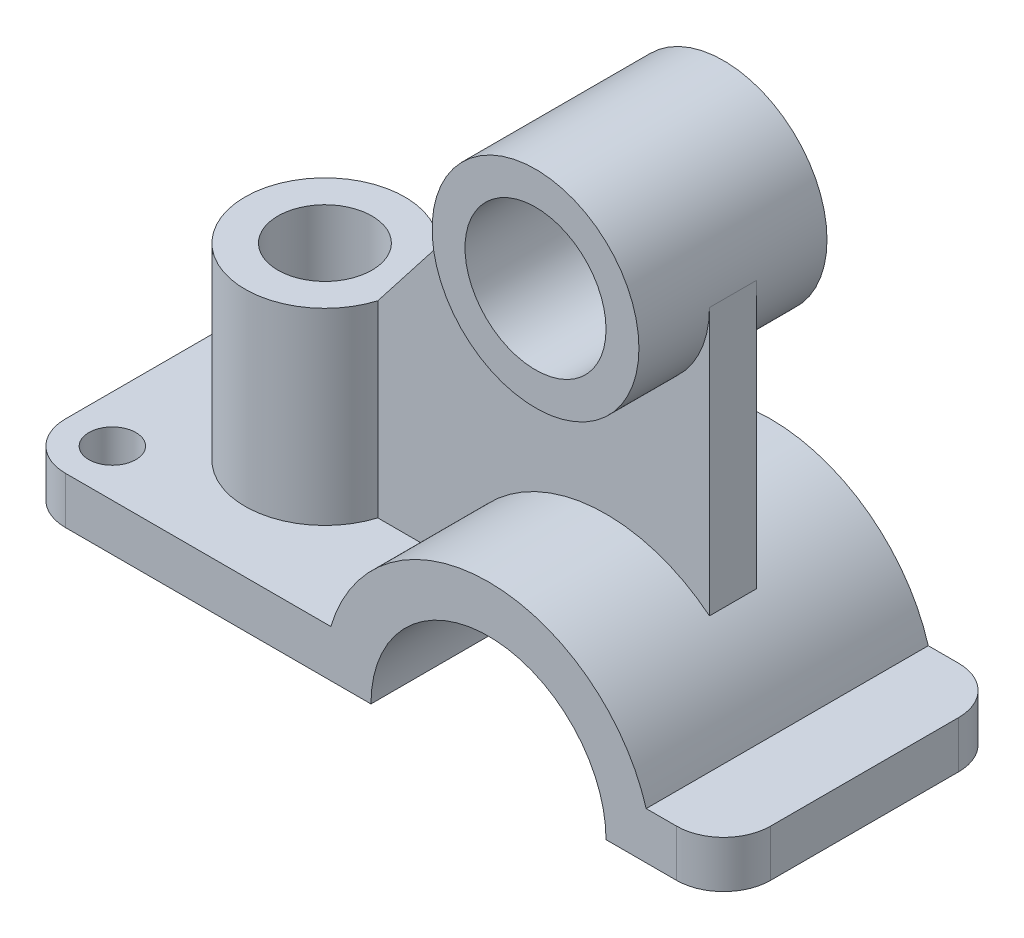
SolidWorks part; units mm, degrees
ref_plane "Front Plane" through (0, 0, 0) normal (0, 0, 1) x (1, 0, 0)
ref_plane "Top Plane" through (0, 0, 0) normal (0, 1, 0) x (1, 0, 0)
ref_plane "Right Plane" through (0, 0, 0) normal (1, 0, 0) x (0, 0, -1)
sketch "Sketch1" plane through (0, 0, 0) normal (0, 0, 1) x (1, 0, 0)
  line L0 (-163.5782, 100) -> (-163.5782, 20)
  line L1 (-180, 0) -> (-200, 0)
  line L2 (-200, 0) -> (-200, 20)
  line L3 (-200, 20) -> (-180, 20)
  line L4 (80, 20) -> (67.082, 20)
  line L5 (-67.082, 20) -> (-180, 20)
  line L6 (50, 0) -> (80, 0)
  line L7 (-180, 0) -> (-50, 0)
  line L8 (100, 20) -> (100, 0)
  line L9 (80, 20) -> (100, 20)
  line L10 (100, 0) -> (80, 0)
  line L11 (-163.5782, 100) -> (-97.082, 100)
  line L12 (-97.082, 20) -> (-97.082, 100)
  line L13 (-97.082, 100) -> (-44, 168.0524)
  line L14 (44, 168.0524) -> (44, 54.4426)
  line L15 (-190, 20) -> (-190, 0) construction
  line L16 (-170, 0) -> (-170, 20) construction
  line L17 (-109.5782, 0) -> (-109.5782, 100) construction
  line L18 (-149.5782, 100) -> (-149.5782, 0) construction
  arc A0 (67.082, 20) -> (-67.082, 20) centre (0, 0) ccw
  arc A1 (50, 0) -> (-50, 0) centre (0, 0) ccw
  circle A2 centre (0, 168.0524) radius 44
  circle A3 centre (0, 168.0524) radius 30
sketch "Sketch2" plane through (0, 0, 0) normal (0, 1, 0) x (1, 0, 0)
  line L0 (-44, -10) -> (-44, -40)
  line L1 (-44, 40) -> (-44, 10)
  line L2 (44, 10) -> (44, 40)
  line L3 (44, -40) -> (44, -10)
  line L4 (44, -40) -> (-44, -40)
  line L5 (-44, -10) -> (-44, 10)
  line L6 (44, -10) -> (44, 10)
  line L7 (44, 40) -> (-44, 40)
  line L8 (-97.082, -10) -> (-44, -10)
  line L9 (-97.082, -10) -> (-97.082, 10)
  line L10 (-97.082, 10) -> (-44, 10)
  line L11 (-67.082, 10) -> (-67.082, 60)
  line L12 (67.082, 60) -> (-67.082, 60)
  line L13 (67.082, -60) -> (67.082, 60)
  line L14 (67.082, -60) -> (-67.082, -60)
  line L15 (-67.082, -60) -> (-67.082, -10)
  line L16 (-200, -40) -> (-200, 40)
  line L17 (-67.082, -60) -> (-180, -60)
  line L18 (-67.082, 60) -> (-180, 60)
  line L19 (100, -40) -> (100, 40)
  line L20 (80, -60) -> (67.082, -60)
  line L21 (80, 60) -> (67.082, 60)
  line L22 (-44, 10) -> (44, 10) construction
  line L23 (-44, -10) -> (44, -10) construction
  line L24 (-50, -60) -> (-50, 60) construction
  line L25 (50, -60) -> (50, 60) construction
  line L26 (-30, 40) -> (-30, -40) construction
  line L27 (30, -40) -> (30, 40) construction
  line L28 (0, 10) -> (0, -10) construction
  circle A0 centre (-129.5782, 0) radius 20
  arc A1 (-97.082, 10) -> (-97.082, -10) centre (-129.5782, 0) ccw
  arc A2 (-200, -40) -> (-180, -60) centre (-180, -40) ccw
  arc A3 (-180, 60) -> (-200, 40) centre (-180, 40) ccw
  circle A4 centre (-180, 40) radius 10
  circle A5 centre (-180, -40) radius 10
  arc A6 (80, -60) -> (100, -40) centre (80, -40) ccw
  arc A7 (100, 40) -> (80, 60) centre (80, 40) ccw
sketch "Sketch3" plane through (0, 0, 0) normal (1, 0, 0) x (0, 0, -1)
  line L0 (34, 20) -> (34, 100)
  line L1 (-34, 100) -> (-34, 20)
  line L2 (-34, 70) -> (-60, 70)
  line L3 (60, 70) -> (34, 70)
  line L4 (10, 124.0524) -> (40, 124.0524)
  line L5 (-40, 124.0524) -> (-10, 124.0524)
  line L6 (40, 212.0524) -> (-40, 212.0524)
  line L7 (40, 0) -> (-40, 0)
  line L8 (40, 20) -> (-40, 20)
  line L9 (-60, 0) -> (-60, 20)
  line L10 (-60, 20) -> (-40, 20)
  line L11 (-40, 0) -> (-60, 0)
  line L12 (60, 20) -> (60, 0)
  line L13 (40, 20) -> (60, 20)
  line L14 (60, 0) -> (40, 0)
  line L15 (-34, 100) -> (34, 100)
  line L16 (10, 168.0524) -> (-10, 168.0524)
  line L17 (-10, 100) -> (-10, 168.0524)
  line L18 (10, 100) -> (10, 168.0524)
  line L19 (60, 70) -> (60, 20)
  line L20 (-60, 70) -> (-60, 20)
  line L21 (-40, 212.0524) -> (-40, 124.0524)
  line L22 (40, 212.0524) -> (40, 124.0524)
  line L23 (-10, 20) -> (-10, 100) construction
  line L24 (10, 20) -> (10, 100) construction
  line L25 (10, 54.4426) -> (-10, 54.4426) construction
  line L26 (-50, 20) -> (-50, 0) construction
  line L27 (-30, 0) -> (-30, 20) construction
  line L28 (30, 20) -> (30, 0) construction
  line L29 (50, 0) -> (50, 20) construction
  line L30 (20, 0) -> (20, 100) construction
  line L31 (-20, 100) -> (-20, 0) construction
  line L32 (-10, 70) -> (-34, 70) construction
  line L33 (34, 70) -> (10, 70) construction
  line L34 (60, 50) -> (-60, 50) construction
  line L35 (-40, 138.0524) -> (40, 138.0524) construction
  line L36 (40, 198.0524) -> (-40, 198.0524) construction
extrude "Boss-Extrude1" add sketch "Sketch1" along normal mid plane 120 contours A1 L6 L10 L8 L9 L4 A0 L5 L3 L2 L1 L7 region at (-130.3301, 16.9194, 0)
extrude "Cut-Extrude5" cut sketch "Sketch2" along normal blind 120 contours A5 | A4 | A0 region at (-129.5782, 0, 0) region at (-180, 0, -40) region at (-180, 0, 40)
extrude "Cut-Extrude8" cut sketch "Sketch2<6>" along normal blind 120 flip side to cut contours A5 | L18 A3 L16 A2 L17 L15 L8 A1 L10 L11 A5 A4 | A0 | L9 A1 A0 | A4 | L10 L9 L8 L5 | L15 L14 L13 L12 L11 L10 L1 L7 L2 L6 L3 L4 L0 L8 | L2 L7 L1 L5 L0 L4 L3 L6 | L19 A7 L21 L13 L20 A6 region at (0, 0, 0) region at (-70.541, 0, 0) region at (-45.8, 0, 25) region at (-68.8728, 0, 35) region at (-162.6271, 0, 0) region at (82.9962, 0, 0) region at (-129.5782, 0, 0) region at (-180, 0, -40) region at (-180, 0, 40)
sketch "Sketch2<6>" plane through (0, 0, 0) normal (0, 1, 0) x (1, 0, 0) same geometry as "Sketch2"
extrude "Boss-Extrude2" add sketch "Sketch1<4>" along normal mid plane 80 separate body contours A2 A3 region at (0, 210.8078, 0)
sketch "Sketch1<4>" plane through (0, 0, 0) normal (0, 0, 1) x (1, 0, 0) same geometry as "Sketch1"
extrude "Boss-Extrude3" add sketch "Sketch2<8>" along normal blind 100 contours L9 A1 A0 region at (-162.6271, 0, 0)
sketch "Sketch2<8>" plane through (0, 0, 0) normal (0, 1, 0) x (1, 0, 0) same geometry as "Sketch2"
extrude "Boss-Extrude4" add sketch "Sketch1<5>" along normal mid plane 20 contours A2 L13 L12 L5 A0 L14 region at (-33.2632, 91.6104, 0)
sketch "Sketch1<5>" plane through (0, 0, 0) normal (0, 0, 1) x (1, 0, 0) same geometry as "Sketch1"
